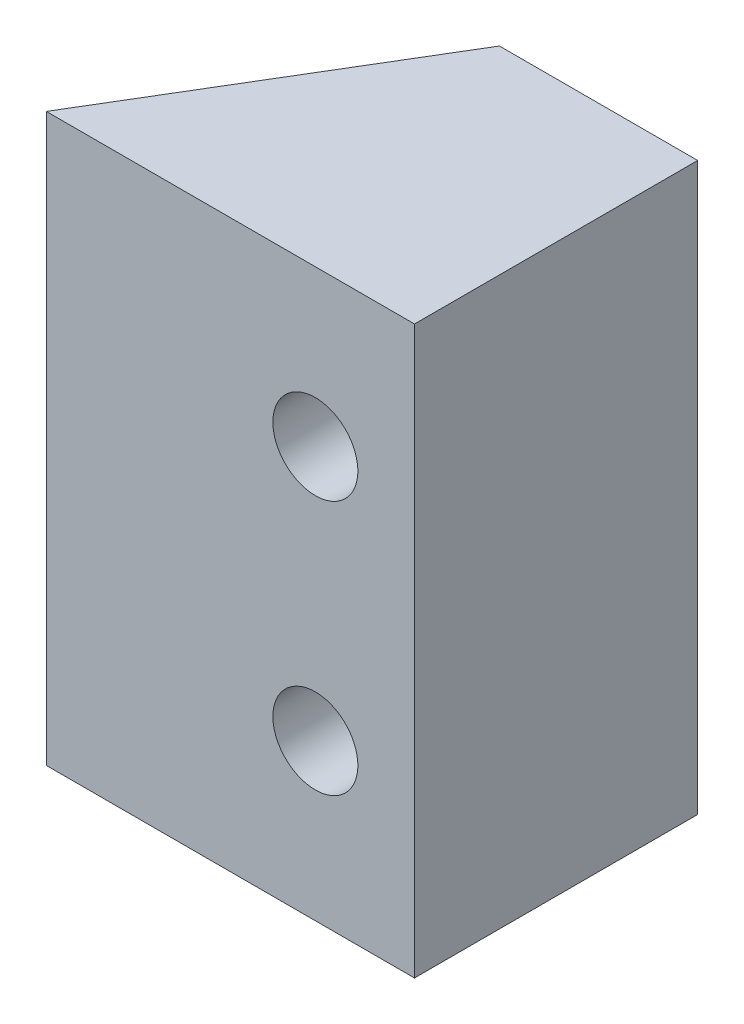
SolidWorks part; units mm, degrees
ref_plane "Front Plane" through (0, 0, 0) normal (0, 0, 1) x (1, 0, 0)
ref_plane "Top Plane" through (0, 0, 0) normal (0, 1, 0) x (1, 0, 0)
ref_plane "Right Plane" through (0, 0, 0) normal (1, 0, 0) x (0, 0, -1)
sketch "Sketch1" plane through (0, 0, 0) normal (0, 1, 0) x (1, 0, 0)
  line L1 (-12.0983, 4.0152) -> (0.9017, 4.0152)
  line L2 (-12.0983, 4.0152) -> (-12.0983, -5.9848)
  line L3 (-12.0983, -5.9848) -> (0.9017, -5.9848)
  line L4 (0.9017, 4.0152) -> (0.9017, -5.9848)
  dimension "D1" = 10
  dimension "D2" = 13
extrude "Boss-Extrude1" add sketch "Sketch1" along normal blind 20
sketch "Sketch3" plane through (0, 0, -4.0152) normal (0, 0, -1) x (-1, 0, 0)
  line L1 (-0.9017, 20) -> (2.5983, 20) construction
  line L2 (-0.9017, 20) -> (-0.9017, 14.5) construction
  line L3 (-0.9017, 14.5) -> (2.5983, 14.5) construction
  line L4 (2.5983, 20) -> (2.5983, 14.5) construction
  line L5 (-0.9017, 0) -> (2.5983, 0) construction
  line L6 (-0.9017, 0) -> (-0.9017, 5.5) construction
  line L7 (-0.9017, 5.5) -> (2.5983, 5.5) construction
  line L8 (2.5983, 0) -> (2.5983, 5.5) construction
  circle A0 centre (2.5983, 5.5) radius 1.5
  circle A1 centre (2.5983, 14.5) radius 1.5
  dimension "D5" = 3
  dimension "D6" = 3
  dimension "D1" = 3.5
  dimension "D2" = 3.5
  dimension "D3" = 5.5
  dimension "D4" = 5.5
extrude "Cut-Extrude1" cut sketch "Sketch3" against normal through all
sketch "Sketch4" plane through (0, 20, 0) normal (0, 1, 0) x (1, 0, 0)
  line L0 (-6.0983, 4.0152) -> (-12.0983, -5.9848)
  line L1 (0.9017, 4.0152) -> (-12.0983, 4.0152) construction
  line L2 (-12.0983, -5.9848) -> (-12.0983, 4.0152)
  line L3 (-12.0983, 4.0152) -> (-6.0983, 4.0152)
  dimension "D1" = 6
extrude "Cut-Extrude2" cut sketch "Sketch4" against normal through all
